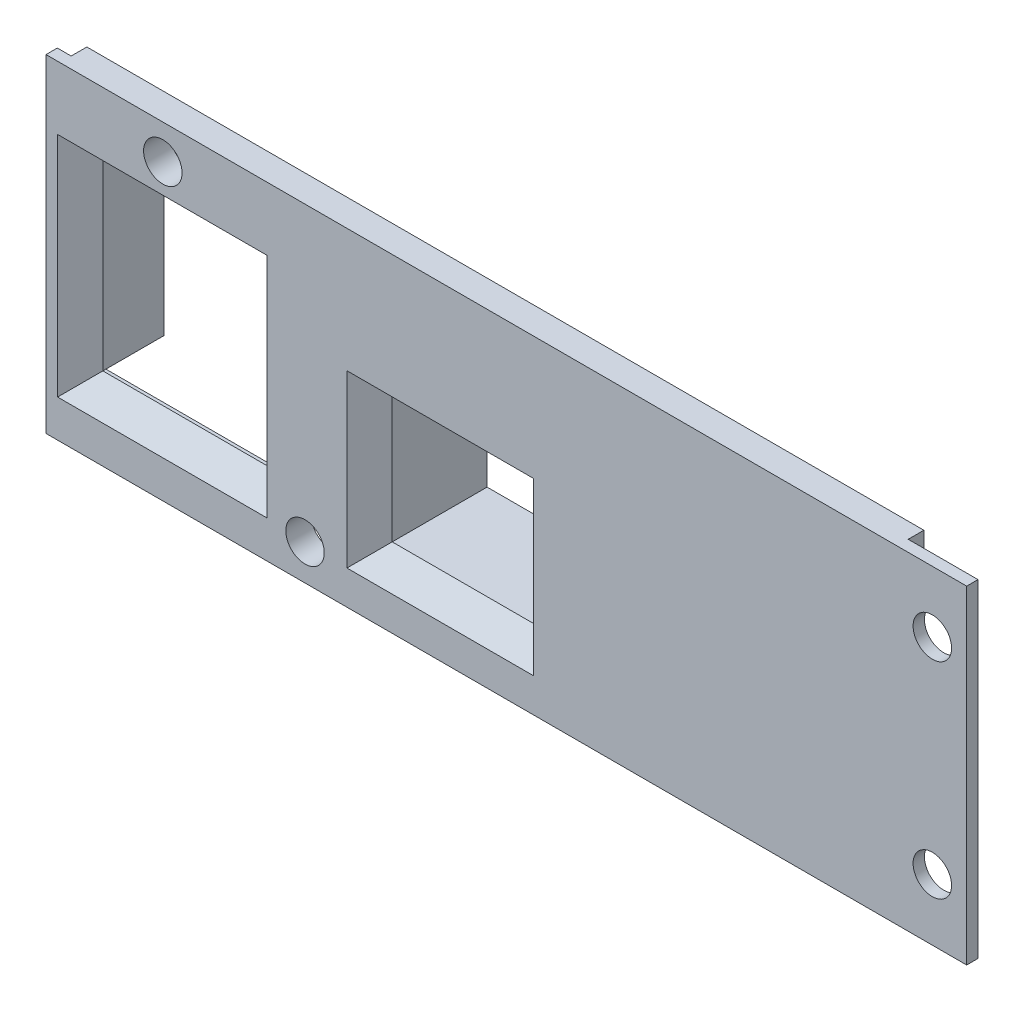
SolidWorks part; units mm, degrees
ref_plane "Front Plane" through (0, 0, 0) normal (0, 0, 1) x (1, 0, 0)
ref_plane "Top Plane" through (0, 0, 0) normal (0, 1, 0) x (1, 0, 0)
ref_plane "Right Plane" through (0, 0, 0) normal (1, 0, 0) x (0, 0, -1)
sketch "Skizze1" plane through (0, 0, 0) normal (0, 0, 1) x (1, 0, 0)
  line L5 (0, 0) -> (0, 29)
  line L6 (0, 29) -> (81.365, 29)
  line L9 (0, 0) -> (81.365, 0)
  line L10 (81.365, 0) -> (81.365, 29)
  line L11 (81.365, 29) -> (81.365, 0) construction
  line L12 (75.2956, 29) -> (81.365, 29) construction
extrude "Aufsatz-Linear austragen1" add sketch "Skizze1" along normal blind 1
sketch "Skizze2" plane through (0, 0, 0) normal (0, 0, -1) x (-1, 0, 0)
  line L1 (-81.365, 29) -> (0, 29) construction
  line L3 (-75.1956, 1.1) -> (-1.2247, 1.1)
  line L4 (-1.2247, 1.1) -> (-1.2247, 29)
  line L5 (-1.2247, 29) -> (-75.1956, 29)
  line L6 (-75.1956, 1.1) -> (-75.1956, 29)
  line L7 (-75.2956, 29) -> (-75.2956, 1) construction
  line L8 (-1.1247, 1) -> (-75.2956, 1) construction
  line L9 (-1.1247, 29) -> (-1.1247, 1) construction
  dimension "D1" = 0.1
  dimension "D2" = 0.1
  dimension "D3" = 0.1
extrude "Aufsatz-Linear austragen2" add sketch "Skizze2" along normal up to vertex (1.3855 mm away)
sketch "Skizze3" plane through (0, 0, -1.3855) normal (0, 0, -1) x (-1, 0, 0)
  line L1 (-77.5859, 16.2496) -> (-19.7247, 16.2496) construction
  line L2 (-58.9956, 16.2496) -> (-41.0956, 16.2496)
  line L4 (-75.1956, 29) -> (-75.1956, 1.1) construction
  line L5 (-41.0956, 4.7) -> (-58.9956, 4.7)
  line L6 (-21.8956, 3.5) -> (-21.8956, 5) construction
  line L7 (-41.0956, 4.7) -> (-41.0956, 16.2496)
  line L9 (-58.9956, 4.7) -> (-58.9956, 16.2496)
  line L10 (-21.7956, 4.7) -> (-75.2956, 4.7) construction
  dimension "D1" = 16.2
  dimension "D2" = 19.2
extrude "Aufsatz-Linear austragen3" add sketch "Skizze3" along normal up to vertex (11.8945 mm away)
sketch "Skizze4" plane through (0, 0, -1.3855) normal (0, 0, -1) x (-1, 0, 0)
  line L5 (-17.5247, 21.4) -> (-3.0247, 21.4)
  line L6 (-3.0247, 21.4) -> (-3.0247, 5.3)
  line L7 (-3.0247, 5.3) -> (-17.5247, 5.3)
  line L8 (-17.5247, 5.3) -> (-17.5247, 21.4)
extrude "Schnitt-Linear austragen1" cut sketch "Skizze4" against normal blind 8
sketch "Skizze5" plane through (0, 0, -1.3855) normal (0, 0, -1) x (-1, 0, 0)
  line L0 (-19.0247, 22.9) -> (-19.0247, 5.3)
  line L2 (-19.0247, 5.3) -> (-17.5247, 5.3)
  line L3 (-17.5247, 5.3) -> (-17.5247, 21.4)
  line L4 (-17.5247, 21.4) -> (-3.0247, 21.4)
  line L5 (-3.0247, 21.4) -> (-3.0247, 5.3)
  line L6 (-3.0247, 5.3) -> (-1.2247, 5.3)
  line L7 (-1.2247, 5.3) -> (-1.2247, 22.9)
  line L9 (-1.2247, 22.9) -> (-19.0247, 22.9)
  line L10 (-1.2247, 1.1) -> (-1.2247, 29) construction
  dimension "D1" = 1.5
  dimension "D2" = 1.5
extrude "Aufsatz-Linear austragen4" add sketch "Skizze5" along normal blind 5
sketch "Skizze6" plane through (0, 0, -1.3855) normal (0, 0, -1) x (-1, 0, 0)
  line L0 (-41.0956, 5) -> (-28.5956, 5)
  line L1 (-28.5956, 5) -> (-28.5956, 16.1)
  line L2 (-28.5956, 16.1) -> (-41.0956, 16.1)
  line L4 (-41.0956, 5) -> (-41.0956, 16.1)
  line L6 (-41.0956, 4.7) -> (-41.0956, 16.2496) construction
  line L7 (-48.7982, 5) -> (-44.2483, 5) construction
  line L9 (-42.8956, 5) -> (-62.7956, 5) construction
  dimension "D1" = 12.5
  dimension "D2" = 11.1
extrude "Schnitt-Linear austragen2" cut sketch "Skizze6" against normal through all
sketch "Skizze7" plane through (0, 0, -1.3855) normal (0, 0, -1) x (-1, 0, 0)
  line L0 (-28.5956, 5) -> (-28.5956, 16.2496)
  line L2 (-26.5956, 16.2496) -> (-26.5956, 3)
  line L5 (-26.5956, 3) -> (-43.0956, 3)
  line L6 (-34.8456, 5) -> (-34.8456, 7.3406) construction
  line L7 (-41.0956, 5) -> (-28.5956, 5) construction
  line L8 (-28.5956, 5) -> (-41.0956, 5)
  line L9 (-41.0956, 16.2496) -> (-43.0956, 16.2496)
  line L11 (-43.0956, 16.2496) -> (-43.0956, 3)
  line L12 (-28.5956, 16.2496) -> (-26.5956, 16.2496)
  line L13 (-41.0956, 5) -> (-41.0956, 16.2496)
  line L14 (-28.5956, 5) -> (-28.5956, 16.1) construction
  line L15 (-10.5179, 16.2496) -> (22.4564, 16.2496) construction
  line L16 (-41.0956, 16.2496) -> (-58.9956, 16.2496) construction
  line L17 (-77.5859, 16.2496) -> (-19.7247, 16.2496) construction
  point P12 (-34.8456, 3)
  dimension "D1" = 2
  dimension "D2" = 2
extrude "Aufsatz-Linear austragen5" add sketch "Skizze7" along normal blind 8
chamfer "Fase2" distance 2 angle 45 8 edges at (3.0247, 13.35, 1) (10.2747, 5.3, 1) (17.5247, 13.35, 1) (10.2747, 21.4, 1) (34.8456, 5, 1) (28.5956, 10.55, 1) (34.8456, 16.1, 1) (41.0956, 10.55, 1)
sketch "Skizze8" plane through (0, 0, 0) normal (0, 0, -1) x (-1, 0, 0)
  circle A0 centre (-78.3303, 23.5848) radius 1.7
  circle A1 centre (-78.3303, 5.4152) radius 1.7
  dimension "D1" = 3.4
extrude "Schnitt-Linear austragen3" cut sketch "Skizze8" against normal blind 12
sketch "Skizze10" plane through (0, 0, -1.3855) normal (0, 0, -1) x (-1, 0, 0)
  line L0 (-1.1247, 5.3) -> (-26.5956, 5.3)
  line L1 (-26.5956, 5.3) -> (-26.5956, 1.1)
  line L2 (-75.1956, 1.1) -> (-1.2247, 1.1) construction
  line L3 (-26.5956, 1.1) -> (-1.2247, 1.1)
  line L4 (-1.2247, 1.1) -> (-1.1247, 5.3)
  line L5 (-26.5956, 3) -> (-26.5956, 16.2496) construction
extrude "Schnitt-Linear austragen5" cut sketch "Skizze10" against normal up to vertex (0.1145 mm away)
sketch "Skizze11" plane through (0, 0, -1.2709) normal (0, 0, -1) x (-1, 0, 0)
  circle A0 centre (-22.891, 3.15) radius 1.7
  dimension "D1" = 3.4
extrude "Schnitt-Linear austragen6" cut sketch "Skizze11" against normal blind 12
chamfer "Fase3" distance 3 angle 45 1 edges at (26.5956, 2.05, -1.3855)
sketch "Skizze12" plane through (0, 0, -1.3855) normal (0, 0, -1) x (-1, 0, 0)
  line L0 (-1.2247, 29) -> (-1.2247, 22.9) construction
  line L3 (-19.4247, 22.9) -> (-19.4247, 29) construction
  line L4 (-1.2247, 29) -> (-75.1956, 29) construction
  line L5 (-1.2247, 25.95) -> (-19.4247, 25.95) construction
  line L6 (-1.2247, 22.9) -> (-1.2247, 29) construction
  circle A0 centre (-10.3247, 25.95) radius 1.7
  dimension "D1" = 3.4
extrude "Schnitt-Linear austragen7" cut sketch "Skizze12" against normal through all
